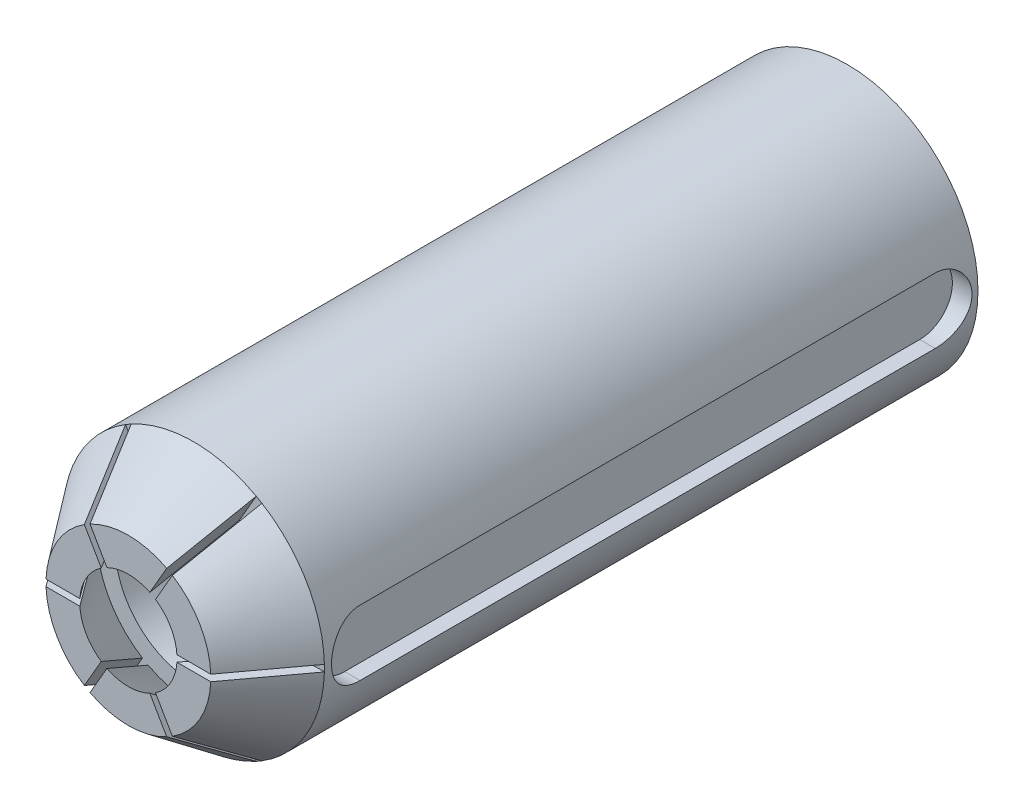
SolidWorks part; units mm, degrees
ref_plane "Front Plane" through (0, 0, 0) normal (1, 0, 0) x (0, 1, 0)
ref_plane "Top Plane" through (0, 0, 0) normal (0, 0, 1) x (0, 1, 0)
ref_plane "Right Plane" through (0, 0, 0) normal (0, 1, 0) x (-1, 0, 0)
sketch "Sketch1" plane through (0, 0, 0) normal (1, 0, 0) x (0, 1, 0)
  line L0 (0, 0) -> (0, 34.3601) construction
  line L10 (-25.4, 127) -> (-16.0197, 139.7)
  line L12 (-25.4, 127) -> (-25.4, 0)
  line L13 (-25.4, 0) -> (-15.24, 0)
  line L14 (-15.24, 0) -> (-15.24, 127)
  line L15 (-15.24, 127) -> (-18.8381, 127)
  line L16 (-18.8381, 127) -> (-9.4579, 139.7)
  line L17 (-9.4579, 139.7) -> (-16.0197, 139.7)
  dimension "D1" = 25.4
  dimension "D2" = 15.24
  dimension "D3" = 12.7
  dimension "D4" = 127
revolve "Revolve1" add sketch "Sketch1" angle 360 about L0
sketch "Sketch3" plane through (0, 0, 0) normal (1, 0, 0) x (0, 1, 0)
  line L0 (0, 139.7) -> (-0.635, 139.7)
  line L1 (9.4579, 139.7) -> (-9.4579, 139.7) construction
  line L2 (-0.635, 139.7) -> (-0.635, 127)
  line L3 (18.8381, 127) -> (-18.8381, 127) construction
  line L4 (-0.635, 127) -> (0.635, 127)
  line L5 (15.24, 127) -> (-15.24, 127) construction
  line L6 (0.635, 127) -> (0.635, 139.7)
  line L7 (0.635, 139.7) -> (0, 139.7)
  dimension "D1" = 0.635
  dimension "D2" = 0.635
extrude "Cut-Extrude1" cut sketch "Sketch3" against normal through all both and the other way through all
pattern_circular "CirPattern1" count 6 over 360 about axis through (0, 0, 139.7) along (0, 0, 1) of "Cut-Extrude1"
thread "Thread1" pitch 1.27 method extrude profile "Thread Profile1" start angle 0, offset 0, length 12.7, pitch 1.27, diameter 30.48
ref_plane "Plane1" through (15.24, 0, 0) normal (0, -1, 0) x (1, 0, 0)
sketch "Thread Profile1" plane through (15.24, 0, 0) normal (0, -1, 0) x (1, 0, 0)
  line L0 (0, 0) -> (0, 1.27) construction
  line L11 (0, 0) -> (0, 1.1112)
  line L12 (0, 1.1112) -> (-0.6874, 0.7144)
  line L13 (-0.6874, 0.7144) -> (-0.6874, 0.3969)
  line L15 (-0.6874, 0.3969) -> (0, 0)
  line L17 (-0.6874, 0.5556) -> (0, 0.5556) construction
  point P2 (0, 0)
  dimension "Pitch" = 1.27
  dimension "Profile_Angle" = 60
  dimension "Profile_Land" = 0.3175
  dimension "Profile_Height" = 0.6874
sketch "Sketch4" plane through (0, 0, 0) normal (1, 0, 0) x (0, 1, 0)
  line L0 (0, 0) -> (0, 128.9505) construction
  line L1 (0, 119.2724) -> (0, 7.5124) construction
  line L2 (6.35, 119.2724) -> (6.35, 7.5124)
  line L3 (-6.35, 119.2724) -> (-6.35, 7.5124)
  arc A0 (6.35, 119.2724) -> (-6.35, 119.2724) centre (0, 119.2724) ccw
  arc A1 (-6.35, 7.5124) -> (6.35, 7.5124) centre (0, 7.5124) ccw
  point P5 (0, 63.3924)
  dimension "D1" = 111.76
  dimension "D2" = 12.7
extrude "Cut-Extrude2" cut sketch "Sketch4" against normal blind 3.81 from offset 25.4
sketch "Sketch5" plane through (0, 0, 0) normal (1, 0, 0) x (0, 1, 0)
  line L0 (0.0482, -14.1614) -> (0.0482, 127.7403) construction
  line L1 (0.0482, 118.9227) -> (0.0482, 7.1627) construction
  line L2 (6.3982, 118.9227) -> (6.3982, 7.1627)
  line L3 (-6.3018, 118.9227) -> (-6.3018, 7.1627)
  arc A0 (6.3982, 118.9227) -> (-6.3018, 118.9227) centre (0.0482, 118.9227) ccw
  arc A1 (-6.3018, 7.1627) -> (6.3982, 7.1627) centre (0.0482, 7.1627) ccw
  point P5 (0.0482, 63.0427)
  dimension "D1" = 111.76
  dimension "D2" = 12.7
extrude "Cut-Extrude3" cut sketch "Sketch5" along normal blind 3.81 from offset 25.4 offset against normal yes
